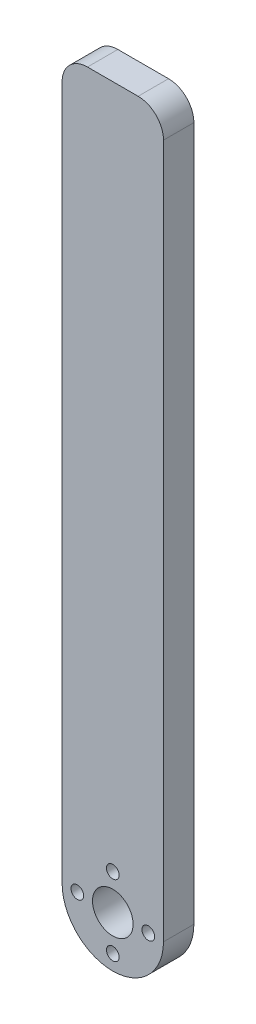
SolidWorks part; units mm, degrees
ref_plane "Front" through (0, 0, 0) normal (0, 0, 1) x (1, 0, 0)
ref_plane "Top" through (0, 0, 0) normal (0, 1, 0) x (1, 0, 0)
ref_plane "Right" through (0, 0, 0) normal (1, 0, 0) x (0, 0, -1)
sketch "Esquisse1" plane through (0, 0, 0) normal (0, 0, 1) x (1, 0, 0)
  line L1 (0, 0) -> (20, 0)
  line L2 (0, 0) -> (0, 152)
  line L3 (0, 152) -> (20, 152)
  line L4 (20, 0) -> (20, 152)
  dimension "D1" = 20
  dimension "D2" = 152
extrude "Boss.-Extru.1" add sketch "Esquisse1" along normal blind 6
sketch "Esquisse2" plane through (0, 0, 6) normal (0, 0, 1) x (1, 0, 0)
  line L0 (10, 0) -> (10, 10) construction
  line L1 (0, 0) -> (20, 0) construction
  line L2 (10, 10) -> (0, 10) construction
  line L3 (0, 152) -> (0, 0) construction
  circle A0 centre (10, 10) radius 4
  dimension "D2" = 8
  dimension "D1" = 10
extrude "Enlèv. mat.-Extru.1" cut sketch "Esquisse2" against normal through all both and the other way through all
fillet "Congé1" radius 10 2 edges at (20, 0, 3) (0, 0, 3)
fillet "Congé2" radius 5 2 edges at (20, 152, 3) (0, 152, 3)
sketch "Esquisse3" plane through (0, 0, 6) normal (0, 0, 1) x (1, 0, 0)
  line L0 (10, 17) -> (10, 10) construction
  circle A0 centre (10, 17) radius 1.25
  circle A1 centre (17, 10) radius 1.25
  circle A2 centre (10, 3) radius 1.25
  circle A3 centre (3, 10) radius 1.25
  point P4 (0.3896, 10.4463)
  point P5 (10, 10)
  point P12 (10, 10)
  dimension "D2" = 2.5
  dimension "D1" = 7
  dimension "D3" = 4
extrude "Enlèv. mat.-Extru.2" cut sketch "Esquisse3" against normal through all both and the other way through all
